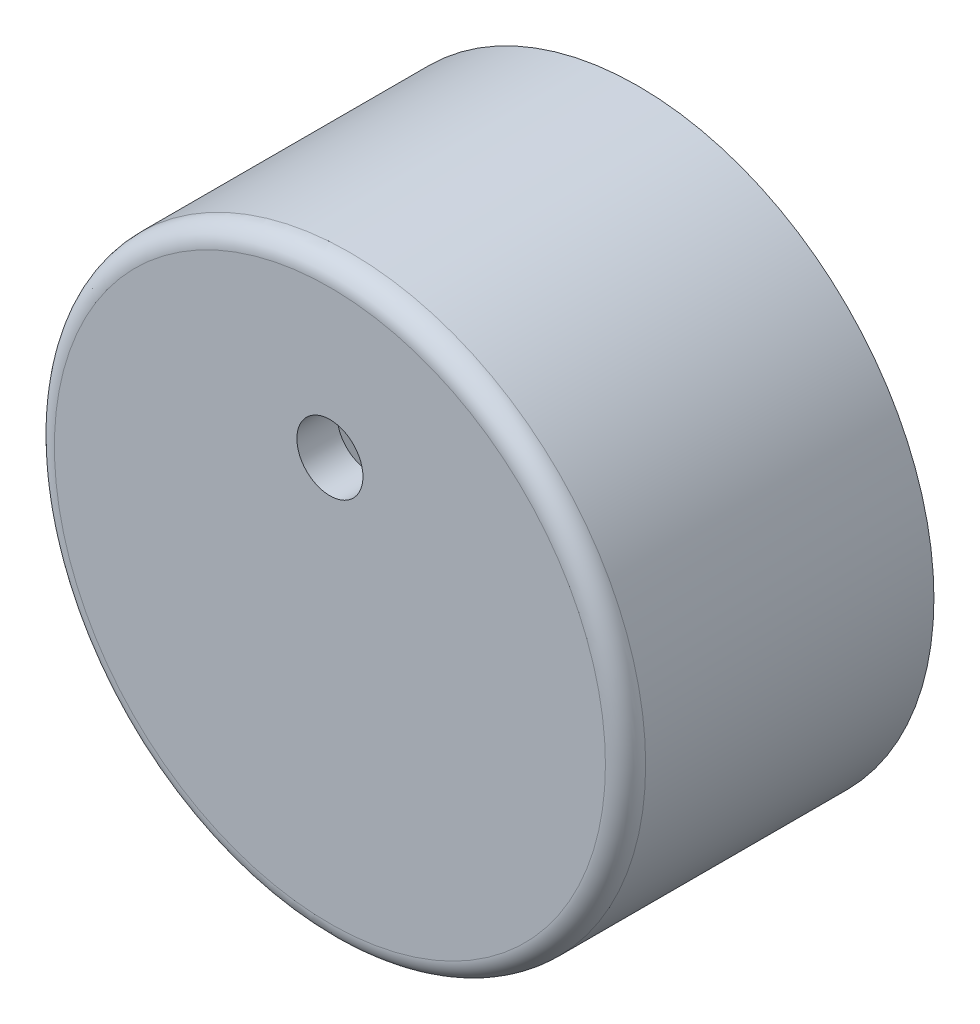
SolidWorks part; units mm, degrees
ref_plane "Front Plane" through (0, 0, 0) normal (0, 0, 1) x (1, 0, 0)
ref_plane "Top Plane" through (0, 0, 0) normal (0, 1, 0) x (1, 0, 0)
ref_plane "Right Plane" through (0, 0, 0) normal (1, 0, 0) x (0, 0, -1)
sketch "Sketch2" plane through (0, 0, 0) normal (0, 0, 1) x (1, 0, 0)
  circle A1 centre (177.5651, -76.6062) radius 41.1
  circle A2 centre (177.5651, -76.6062) radius 44.1
  dimension "D1" = 82.2
  dimension "D2" = 3
extrude "Boss-Extrude1" add sketch "Sketch2" along normal blind 40
sketch "Sketch3" plane through (0, 0, 40) normal (0, 0, 1) x (1, 0, 0)
  circle A0 centre (177.5651, -76.6062) radius 44.1 construction
  circle A1 centre (177.5651, -76.6062) radius 44.1
extrude "Boss-Extrude2" add sketch "Sketch3" along normal blind 6
fillet "Fillet1" radius 7 1 edges at (218.6651, -76.6062, 40)
fillet "Fillet2" radius 3 1 edges at (221.6651, -76.6062, 46)
sketch "Sketch4" plane through (0, 0, 0) normal (0, 0, 1) x (1, 0, 0)
  line L0 (177.5651, -35.5062) -> (177.5651, -117.7062) construction
  line L2 (218.6651, -76.6062) -> (136.4651, -76.6062) construction
  circle A0 centre (177.5651, -76.6062) radius 41.1 construction
  circle A1 centre (177.5651, -57.5062) radius 4.93
  circle A2 centre (177.5651, -57.5062) radius 6.93
  dimension "D2" = 9.86
  dimension "D3" = 2
  dimension "D1" = 22
ref_plane "Plane1" through (0, 0, 61) normal (0, 0, 1) x (1, 0, 0)
sketch "Sketch5" plane through (0, 0, 61) normal (0, 0, 1) x (1, 0, 0)
  circle A4 centre (177.5651, -57.2312) radius 3.25
  circle A5 centre (177.5651, -57.2312) radius 4.25
  dimension "D1" = 6.5
  dimension "D2" = 8.5
sketch "Sketch7" plane through (0, 0, 46) normal (0, 0, 1) x (1, 0, 0)
  circle A0 centre (177.5651, -57.5062) radius 6.93 construction
  circle A1 centre (177.5651, -57.5062) radius 6.93
  circle A2 centre (177.5651, -57.5062) radius 4.93 construction
  circle A3 centre (177.5651, -57.5062) radius 4.93
loft "Loft2" add section "Sketch7" section "Sketch5" connector at (181.7642, -51.9932, 46) connector at (181.5565, -55.7715, 61)
loft "Cut-Loft2" cut section "Sketch7<4>" section "Sketch5<6>" connector at (178.5132, -52.6682, 46) connector at (180.7863, -56.7995, 61)
sketch "Sketch7<4>" plane through (0, 0, 46) normal (0, 0, 1) x (1, 0, 0) same geometry as "Sketch7"
sketch "Sketch5<6>" plane through (0, 0, 61) normal (0, 0, 1) x (1, 0, 0) same geometry as "Sketch5"
extrude "Cut-Extrude1" cut sketch "Sketch7<5>" against normal up to next (6 mm away) contours A3 region at (177.5651, -57.5062, 46)
sketch "Sketch7<5>" plane through (0, 0, 46) normal (0, 0, 1) x (1, 0, 0) same geometry as "Sketch7"
delete or keep bodies "Body-Delete/Keep 1" type delete bodies bodies 108
